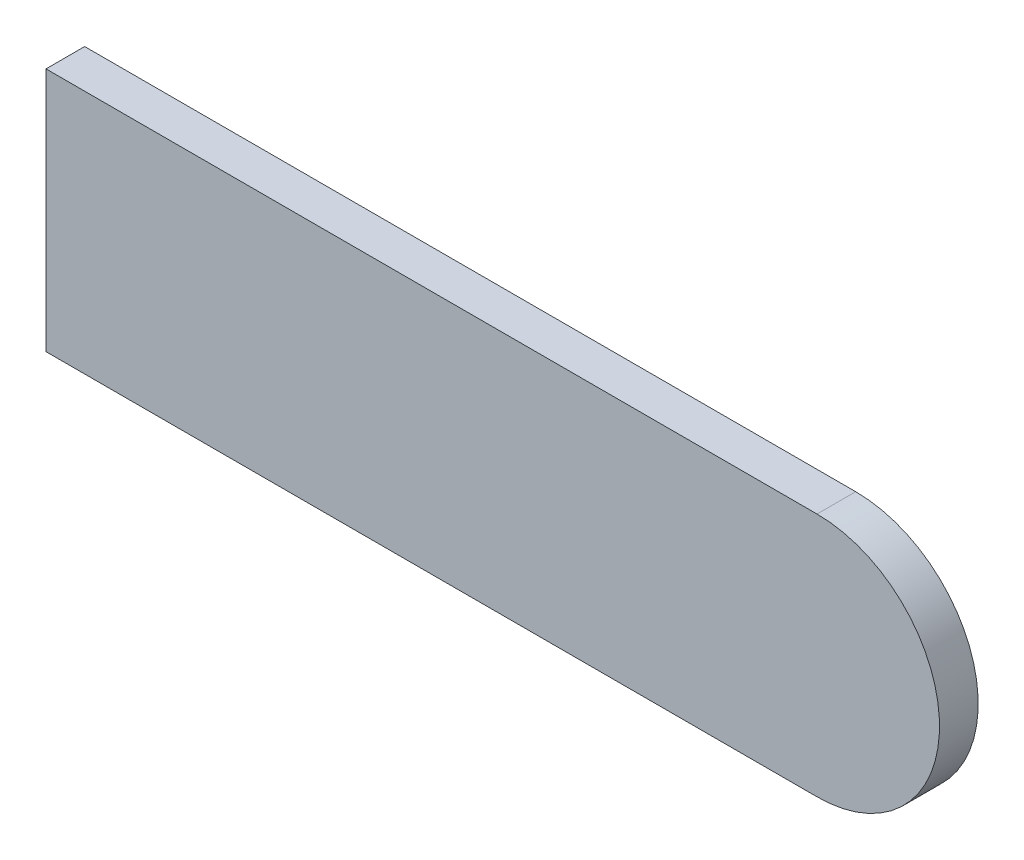
SolidWorks part; units mm, degrees
ref_plane "Front Plane" through (0, 0, 0) normal (0, 0, 1) x (1, 0, 0)
ref_plane "Top Plane" through (0, 0, 0) normal (0, 1, 0) x (1, 0, 0)
ref_plane "Right Plane" through (0, 0, 0) normal (1, 0, 0) x (0, 0, -1)
sketch "Sketch1" plane through (0, 0, 0) normal (0, 0, 1) x (1, 0, 0)
  line L0 (-59.8106, 0) -> (18.2346, 0) construction
  line L1 (-59.8106, -9.5) -> (0, -9.5)
  line L2 (-59.8106, 9.5) -> (-59.8106, -9.5)
  line L3 (-59.8106, 9.5) -> (0, 9.5)
  line L4 (-59.8106, -3.5) -> (-59.8106, 3.5) construction
  line L11 (-22.9306, 9.5) -> (-522.9306, 9.5) construction
  arc A0 (0, -9.5) -> (0, 9.5) centre (0, 0) ccw
extrude "Boss-Extrude1" add sketch "Sketch1" along normal blind 3
